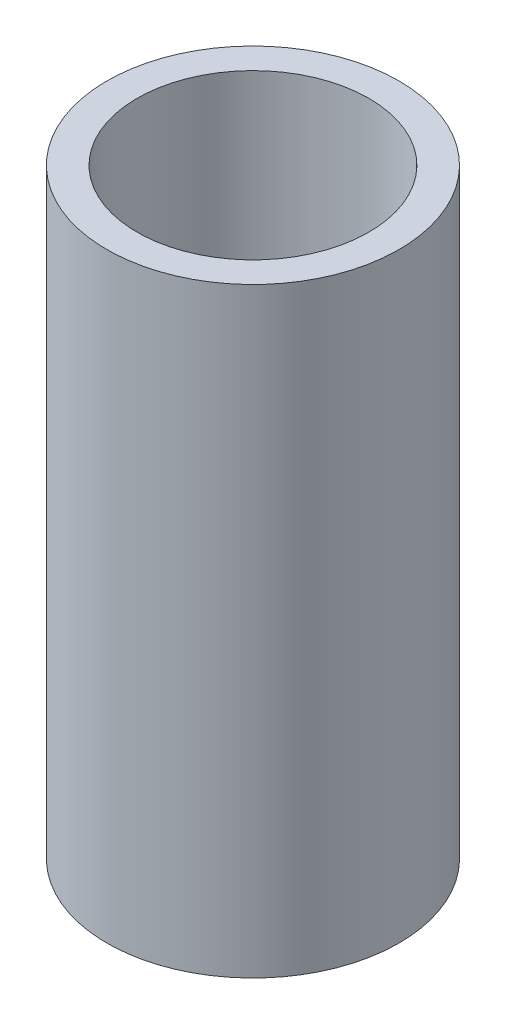
SolidWorks part; units mm, degrees
ref_plane "Front Plane" through (0, 0, 0) normal (0, 0, 1) x (1, 0, 0)
ref_plane "Top Plane" through (0, 0, 0) normal (0, 1, 0) x (1, 0, 0)
ref_plane "Right Plane" through (0, 0, 0) normal (1, 0, 0) x (0, 0, -1)
sketch "Sketch1" plane through (0, 0, 0) normal (0, 1, 0) x (1, 0, 0)
  circle A0 centre (0, 0) radius 3.175
  circle A1 centre (0, 0) radius 4
  dimension "D1" = 6.35
  dimension "D2" = 8
extrude "Boss-Extrude1" add sketch "Sketch1" along normal blind 16.448
